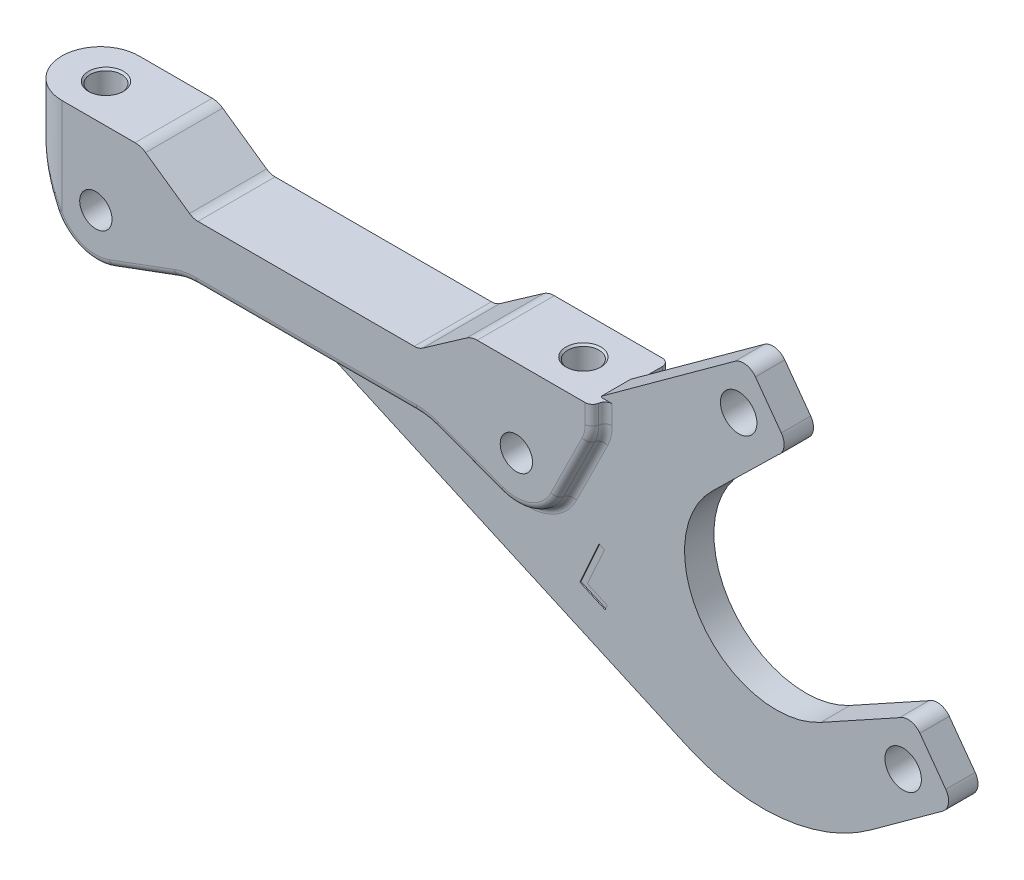
SolidWorks part; units mm, degrees
material "6061-T6 (SS)"
ref_plane "Front Plane" through (0, 0, 0) normal (0, 0, 1) x (1, 0, 0)
ref_plane "Top Plane" through (0, 0, 0) normal (0, 1, 0) x (1, 0, 0)
ref_plane "Right Plane" through (0, 0, 0) normal (1, 0, 0) x (0, 0, -1)
sketch "Sketch1" plane through (0, 0, 0) normal (0, 0, 1) x (1, 0, 0)
  line L0 (-62, 15.9233) -> (-62, -14.304) construction
  line L1 (62, 13.7642) -> (62, -21.0511) construction
  line L2 (-68.4547, -5.5412) -> (-78, 13.76)
  line L3 (-78, 13.76) -> (78, 13.76)
  line L4 (78, 13.76) -> (68.4547, -5.5412)
  line L5 (-73.8283, -12.5) -> (71.5637, -12.5) construction
  line L6 (-26.3177, -4.24) -> (18.9734, -4.24) construction
  line L7 (-30, -4.24) -> (30, -4.24)
  line L8 (-52.9127, -11.7234) -> (-35.2048, -5.1719)
  line L9 (35.2048, -5.1719) -> (52.9127, -11.7234)
  circle A0 centre (-57.25, 0) radius 4.75 construction
  circle A1 centre (57.25, 0) radius 4.75 construction
  arc A2 (-68.4547, -5.5412) -> (-52.9127, -11.7234) centre (-57.25, 0) ccw
  arc A3 (52.9127, -11.7234) -> (68.4547, -5.5412) centre (57.25, 0) ccw
  arc A4 (35.2048, -5.1719) -> (30, -4.24) centre (30, -19.24) ccw
  arc A5 (-30, -4.24) -> (-35.2048, -5.1719) centre (-30, -19.24) ccw
  point P13 (0, 0)
  point P21 (0, 0)
  dimension "D1" = 9.5
  dimension "D2" = 9.5
  dimension "D5" = 25
  dimension "D11" = 15
  dimension "D3" = 124
  dimension "D9" = 156
  dimension "D12" = 60
  dimension "D13" = 30
  dimension "D4" = 62
  dimension "D6" = 18
  dimension "D7" = 26.26
extrude "Boss-Extrude2" add sketch "Sketch1" along normal blind 21
ref_plane "Hub Mounting Plane" through (0, 0, 57) normal (0, 0, 1) x (1, 0, 0)
sketch "Sketch2" plane through (0, 13.76, 0) normal (0, 1, 0) x (1, 0, 0)
  line L0 (78, -21) -> (78, 0) construction
  line L1 (-78, -21) -> (78, -21)
  line L2 (-78, -21) -> (-78, 0)
  line L3 (-78, 0) -> (78, 0)
  line L4 (78, -21) -> (78, 0)
  line L5 (-78, -21) -> (-78, 0) construction
  line L6 (78, -21) -> (-78, -21) construction
  line L7 (78.3439, -10.5) -> (-79.2862, -10.5) construction
  line L8 (78, 0) -> (-78, 0) construction
  circle A0 centre (-65, -10.5) radius 5.05 construction
  circle A1 centre (65, -10.5) radius 5.05 construction
  point P6 (0, 0)
  dimension "D2" = 10.1
  dimension "D3" = 10.1
  dimension "D4" = 130
  dimension "D5" = 65
  dimension "D1" = 10.5
  dimension "D6" = 21
extrude "Boss-Extrude3" add sketch "Sketch2" along normal blind 7.5
fillet "Fillet1" [suppressed] radius 10
sketch "Sketch3" [suppressed] plane through (0, 0, 0) normal (0, 0, -1) x (-1, 0, 0)
  line L0 (-71.9881, 4.5) -> (69.3283, 4.5)
  line L1 (-67.7059, -12.5) -> (67.0774, -12.5) construction
  circle A0 centre (-57.25, 0) radius 4.75
  circle A1 centre (57.25, 0) radius 4.75
  circle A2 centre (-57.25, 0) radius 12.5
  circle A3 centre (57.25, 0) radius 12.5
  arc A4 (-68.4547, -5.5412) -> (-52.9127, -11.7234) centre (-57.25, 0) ccw construction
  dimension "D1" = 17
ref_plane "Plane1" through (0, 0, 0) normal (0, 0, -1) x (-1, 0, 0)
sketch "Sketch5" plane through (0, 21.26, 0) normal (0, 1, 0) x (1, 0, 0)
  circle A0 centre (65, -10.5) radius 5.05 construction
  circle A1 centre (-65, -10.5) radius 5.05 construction
  circle A2 centre (65, -10.5) radius 5.05 construction
  circle A3 centre (-65, -10.5) radius 5.05 construction
sketch "Sketch6" plane through (0, 0, 0) normal (0, 0, -1) x (-1, 0, 0)
  line L2 (29.4573, 11.26) -> (-29.4573, 11.26)
  line L4 (-78, 21.26) -> (78, 21.26) construction
  line L5 (31.7516, 11.9834) -> (45, 21.26)
  line L6 (-45, 21.26) -> (-31.7516, 11.9834)
  line L7 (-45, 21.26) -> (45, 21.26)
  arc A0 (31.7516, 11.9834) -> (29.4573, 11.26) centre (29.4573, 15.26) cw
  arc A1 (-29.4573, 11.26) -> (-31.7516, 11.9834) centre (-29.4573, 15.26) cw
  dimension "D4" = 4
  dimension "D2" = 145
  dimension "D3" = 145
  dimension "D1" = 90
  dimension "D5" = 45
  dimension "D6" = 10
extrude "Cut-Extrude3" cut sketch "Sketch6" against normal up to surface (21 mm away) up to face at (0, 0.932, 21)
fillet "Fillet3" radius 5 2 edges at (-45, 21.26, 10.5) (45, 21.26, 10.5)
fillet "Fillet4" radius 10 2 edges at (-78, 13.76, 10.5) (78, 13.76, 10.5)
sketch "Sketch8" plane through (0, 21.26, 0) normal (0, 1, 0) x (1, 0, 0)
  line L1 (-78, 0) -> (-78, -21)
  line L6 (-65, -10.5) -> (-66.5, -10.5) construction
  line L9 (-77, -0.6837) -> (-77, -19.879) construction
  line L10 (-66.5, 0) -> (-78, 0)
  line L11 (-78, -21) -> (-66.5, -21)
  line L12 (0, 15.9579) -> (0, -40.4638) construction
  arc A5 (-66.5, 0) -> (-66.5, -21) centre (-66.5, -10.5) ccw
  point P6 (-65.75, -10.5)
  dimension "D1" = 12
extrude "Cut-Extrude4" cut sketch "Sketch8" against normal blind 34
hole_wizard "M10x1.5 Tapped Hole2" positions "3DSketch3" profile "Sketch12" tap size "M10x1.5" standard "ANSI Metric"
sketch3d "3DSketch3"
  point P0 (65, 21.26, 10.5)
  point P3 (-65, 21.26, 10.5)
  point P5 (-65, 21.26, 10.5)
  point P7 (-65, 21.26, 10.5)
cosmetic thread "Hole Thread5" parameters "D1"=20, "D2"=10
cosmetic thread "Hole Thread6" parameters "D1"=20, "D2"=10
cosmetic thread "Hole Thread7" parameters "D1"=20, "D2"=10
cosmetic thread "Hole Thread8" parameters "D1"=20, "D2"=10
sketch "Sketch12" plane through (65, 21.26, 10.5) normal (1, 0, 0) x (0, 0, 1)
  line L0 (0, 0) -> (0, 16.0537)
  line L1 (0, 16.0537) -> (4.25, 13.5)
  line L2 (4.25, 13.5) -> (4.25, 0)
  line L5 (4.25, 0) -> (0, 0)
  line L10 (0, 16.0537) -> (-4.25, 13.5) construction
  line L11 (0, -6.35) -> (0, 107.95) construction
  dimension "Tap Drill Dia." = 8.5
  dimension "Tap Drill Depth" = 13.5
  dimension "Drill Angle" = 118
chamfer "Chamfer2" distance 0.5 angle 45 2 edges at (-65, 21.26, 14.75) (65, 21.26, 14.75)
hole_wizard "M10x1.25 Tapped Hole1" positions "Sketch17" profile "Sketch18" tap size "M10x1.25" standard "ANSI Metric" end condition through all
sketch "Sketch17" plane through (0, 0, 0) normal (0, 0, -1) x (-1, 0, 0)
  point P0 (-57.25, 0)
  point P3 (57.25, 0)
sketch "Sketch18" plane through (57.25, 0, 0) normal (1, 0, 0) x (0, 1, 0)
  line L0 (0, 0) -> (0, 21)
  line L1 (0, 21) -> (4.4, 21)
  line L2 (4.4, 21) -> (4.4, 0)
  line L5 (4.4, 0) -> (0, 0)
  line L11 (0, -6.35) -> (0, 107.95) construction
  dimension "Thru Tap Drill Dia." = 8.8
  dimension "Thru Tap Drill Depth" = 21
cosmetic thread "Hole Thread3" parameters "D2"=10
cosmetic thread "Hole Thread10" parameters "D2"=10
ref_plane "Plane3" through (0, 0, 9.6) normal (0, 0, 1) x (1, 0, 0)
chamfer "Chamfer3" distance 0.5 angle 45 2 edges at (-61.65, 0, 0) (52.85, 0, 0)
sketch "Sketch19" plane through (0, 0, 9.6) normal (0, 0, 1) x (1, 0, 0)
  line L3 (100.4018, -49.281) -> (0, -4.24)
  line L8 (125.9954, 37.394) -> (118.942, 47.1022)
  line L10 (77, 33.4551) -> (77, 21.26) construction
  line L14 (58.8815, -52.0577) -> (191.3568, 45.5598) construction
  line L15 (69.75, 21.26) -> (60.25, 21.26) construction
  line L19 (113.3548, 47.9871) -> (77, 21.5738)
  line L22 (158.144, -13.66) -> (136.7247, -25.4871)
  line L23 (170.7846, -24.2531) -> (163.7312, -14.5449)
  line L24 (171.821, -32.4848) -> (154.5369, -8.6953) construction
  line L25 (169.8997, -29.8403) -> (150.2564, -44.112)
  line L26 (125.1105, 31.8068) -> (107.1704, 14.2812)
  line L27 (128.9273, -14.7549) -> (169.2983, -70.3208) construction
  line L28 (77, 21.5738) -> (77, 21.26)
  line L29 (77, 21.26) -> (78, 21.26)
  line L30 (78, 21.26) -> (78, 16.0976)
  line L31 (78, 21.26) -> (78, 16.0976) construction
  line L32 (68.4547, -5.5412) -> (76.9637, 11.6646)
  line L33 (68.4547, -5.5412) -> (76.9637, 11.6646) construction
  line L34 (52.9127, -11.7234) -> (35.2048, -5.1719)
  line L35 (35.2048, -5.1719) -> (52.9127, -11.7234) construction
  line L36 (-30, -4.24) -> (30, -4.24) construction
  line L37 (0, 6.1197) -> (0, -13.66) construction
  line L38 (0, -4.24) -> (30, -4.24)
  arc A0 (170.2177, -3.8157) -> (138.204, 40.2475) centre (65.9033, -45.9433) ccw construction
  arc A5 (107.1704, 14.2812) -> (136.7247, -25.4871) centre (124.6402, -3.6018) ccw
  circle A10 centre (159.1678, -25.2769) radius 5 construction
  arc A12 (163.7312, -14.5449) -> (158.144, -13.66) centre (160.4952, -16.896) ccw
  circle A13 centre (114.3785, 36.3702) radius 5 construction
  arc A18 (113.3548, 47.9871) -> (118.942, 47.1022) centre (115.7059, 44.7511) cw
  arc A20 (170.7846, -24.2531) -> (169.8997, -29.8403) centre (167.5486, -26.6042) cw
  arc A21 (100.4018, -49.281) -> (150.2564, -44.112) centre (120.8672, -3.6611) ccw
  arc A22 (125.9954, 37.394) -> (125.1105, 31.8068) centre (122.7593, 35.0428) cw
  arc A23 (76.9637, 11.6646) -> (78, 16.0976) centre (68, 16.0976) ccw
  arc A24 (76.9637, 11.6646) -> (78, 16.0976) centre (68, 16.0976) ccw construction
  arc A25 (52.9127, -11.7234) -> (68.4547, -5.5412) centre (57.25, 0) ccw
  arc A26 (52.9127, -11.7234) -> (68.4547, -5.5412) centre (57.25, 0) ccw construction
  arc A27 (35.2048, -5.1719) -> (30, -4.24) centre (30, -19.24) ccw
  arc A28 (35.2048, -5.1719) -> (30, -4.24) centre (30, -19.24) ccw construction
  point P20 (156.9177, 20.1825)
  dimension "D2" = 4
  dimension "D4" = 50
  dimension "D3" = 4
  dimension "D8" = 4
  dimension "D9" = 4
  dimension "D6" = 25
  dimension "D10" = 10
  dimension "D7" = 10
  dimension "D12" = 10
  dimension "D5" = 10
  dimension "D11" = 20
  dimension "D13" = 20
  dimension "D14" = 12
extrude "Boss-Extrude4" add sketch "Sketch19" along normal blind 8
sketch "Sketch26" plane through (0, 0, 17.6) normal (0, 0, 1) x (1, 0, 0)
  line L0 (70, -24.6823) -> (133.8678, -53.3339) construction
  line L2 (0, -4.24) -> (100.4018, -49.281) construction
  line L3 (0, -4.24) -> (100.4018, -49.281) construction
  text T1 "L" font "Tahoma" height in points 48
  point P5 (0, 0)
  point P7 (0, 0)
  dimension "D1" = 10
  dimension "D2" = 70
  dimension "D3" = 40
extrude "Cut-Extrude7" cut sketch "Sketch26" against normal blind 0.3
hole_wizard "7/16-20 Tapped Hole1" positions "Sketch35" profile "Sketch36" tap size "7/16-20" standard "ANSI Inch" end condition through all
sketch "Sketch35" plane through (0, 0, 17.6) normal (0, 0, 1) x (1, 0, 0)
  point P0 (114.3785, 36.3702)
  point P2 (159.1678, -25.2769)
sketch "Sketch36" plane through (114.3785, 36.3702, 17.6) normal (1, 0, 0) x (0, -1, 0)
  line L0 (0, 0) -> (0, 17.6)
  line L1 (0, 17.6) -> (4.9606, 17.6)
  line L2 (4.9606, 17.6) -> (4.9606, 0)
  line L5 (4.9606, 0) -> (0, 0)
  line L11 (0, -6.35) -> (0, 107.95) construction
  dimension "Thru Tap Drill Dia." = 9.9212
  dimension "Thru Tap Drill Depth" = 17.6
cosmetic thread "Hole Thread11" parameters "D1"=22.23, "D2"=10.9212
cosmetic thread "Hole Thread12" parameters "D1"=22.23, "D2"=10.9212
chamfer "Chamfer4" distance 0.5 angle 45 2 edges at (154.2071, -25.2769, 9.6) (109.4179, 36.3702, 9.6)
fillet "Fillet29" radius 2 25 edges at (78, 18.6788, 0) (77.7375, 13.8214, 0) (72.7092, 3.0617, 0) (61.8701, -11.6149, 0) (44.0587, -8.4477, 0) (32.6438, -4.4748, 0) (0, -4.24, 0) (-32.6438, -4.4748, 0) (-44.0587, -8.4477, 0) (-60.2135, -12.1436, 0) (-74.3009, 6.2803, 3.4718) (-74.3009, 6.2803, 17.5282) (-60.2135, -12.1436, 21) (-44.0587, -8.4477, 21) (-32.6438, -4.4748, 21) (78, 18.6788, 21) (77.7375, 13.8214, 21) (72.7092, 3.0617, 21) (61.8701, -11.6149, 21) (44.0587, -8.4477, 21) (32.6438, -4.4748, 21) (0, -4.24, 21)
fillet "Fillet30" radius 2 7 edges at (78, 18.6788, 9.6) (77.7375, 13.8214, 9.6) (32.6438, -4.4748, 9.6) (44.0587, -8.4477, 9.6) (61.8701, -11.6149, 9.6) (72.7092, 3.0617, 9.6) (15, -4.24, 9.6)
fillet "Fillet31" radius 2 7 edges at (78, 18.6788, 17.6) (77.7375, 13.8214, 17.6) (32.6438, -4.4748, 17.6) (44.0587, -8.4477, 17.6) (61.8701, -11.6149, 17.6) (72.7092, 3.0617, 17.6) (15, -4.24, 17.6)
equation "\"D4@Sketch1\"=\"D3@Sketch1\"/2"
equation "\"D5@Sketch2\"=\"D4@Sketch2\"/2"
equation "\"D13@Sketch1\"=\"D12@Sketch1\"/2"
equation "\"D5@Sketch6\"=\"D1@Sketch6\"/2"
equation "\"D1@Sketch2\"=\"D6@Sketch2\"/2"
equation "\"D8@Sketch19\"=\"D3@Sketch19\""
equation "\"D9@Sketch19\"=\"D2@Sketch19\""
equation "\"D12@Sketch19\"=\"D10@Sketch19\""
equation "\"D13@Sketch19\"=\"D11@Sketch19\""
equation "\"D4@Sketch19\"=\"D6@Sketch19\"*2"
